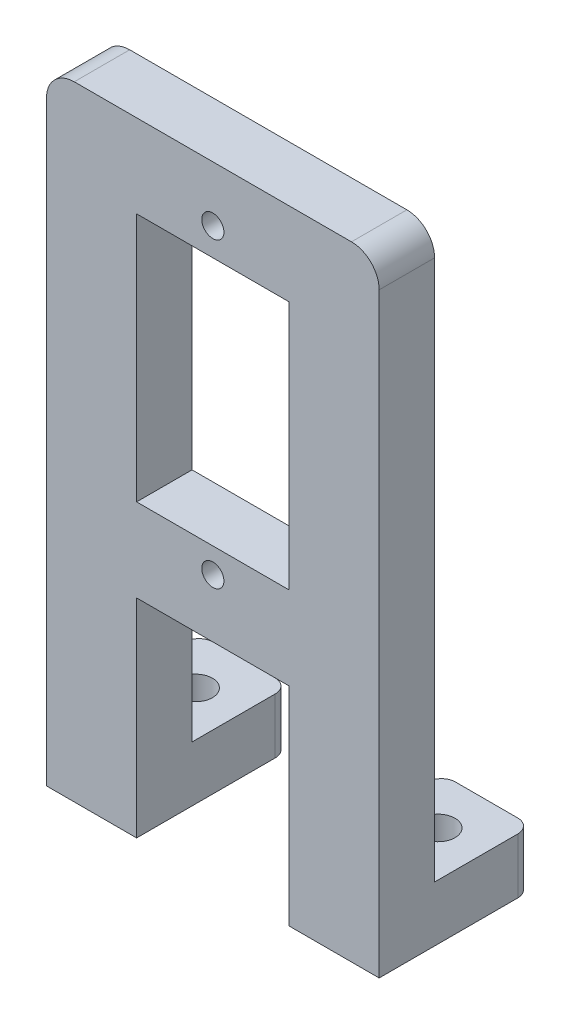
SolidWorks part; units mm, degrees
ref_plane "Front Plane" through (0, 0, 0) normal (0, 0, 1) x (1, 0, 0)
ref_plane "Top Plane" through (0, 0, 0) normal (0, 1, 0) x (1, 0, 0)
ref_plane "Right Plane" through (0, 0, 0) normal (1, 0, 0) x (0, 0, -1)
sketch "Sketch1" plane through (0, 0, 0) normal (0, 0, 1) x (1, 0, 0)
  line L0 (-15.24, -19.05) -> (-15.24, -38.1)
  line L1 (-6.985, 11.43) -> (6.985, 11.43)
  line L2 (-6.985, 11.43) -> (-6.985, -11.43)
  line L3 (-6.985, -11.43) -> (6.985, -11.43)
  line L4 (6.985, 11.43) -> (6.985, -11.43)
  line L5 (-15.24, 19.05) -> (15.24, 19.05)
  line L6 (-15.24, 19.05) -> (-15.24, -19.05)
  line L7 (-15.24, -19.05) -> (15.24, -19.05)
  line L8 (15.24, 19.05) -> (15.24, -19.05)
  line L9 (-15.24, -38.1) -> (-6.985, -38.1)
  line L10 (-6.985, -38.1) -> (-6.985, -19.05)
  line L11 (-15.24, -19.05) -> (-6.985, -19.05)
  line L12 (15.24, -19.05) -> (15.24, -38.1)
  line L13 (15.24, -38.1) -> (6.985, -38.1)
  line L14 (6.985, -38.1) -> (6.985, -19.05)
  line L15 (6.985, -19.05) -> (15.24, -19.05)
  point P5 (0, 11.43)
  point P6 (-6.985, 0)
  point P12 (0, 19.05)
  point P13 (-15.24, 0)
  dimension "D1" = 13.97
  dimension "D2" = 22.86
  dimension "D3" = 30.48
  dimension "D4" = 38.1
  dimension "D5" = 19.05
extrude "Boss-Extrude1" add sketch "Sketch1" along normal blind 5.08 contours L6 L5 L8 L7 | L11 L10 L9 L0 | L12 L13 L14 L15 | L2 L1 L4 L3
fillet "Fillet1" radius 2.54 2 edges at (15.24, 19.05, 2.54) (-15.24, 19.05, 2.54)
ref_plane "Plane1" through (0, -38.1, 0) normal (0, 1, 0) x (1, 0, 0)
sketch "Sketch3" plane through (0, -38.1, 0) normal (0, 1, 0) x (1, 0, 0)
  line L0 (-15.24, 0) -> (-15.24, 8.89)
  line L1 (-15.24, 8.89) -> (-6.985, 8.89)
  line L2 (-6.985, 8.89) -> (-6.985, 0)
  line L3 (-12.7, 0) -> (12.7, 0) construction
  line L4 (-6.985, 0) -> (-15.24, 0)
  line L5 (-15.24, 0) -> (-6.985, 0) construction
  dimension "D2" = 8.89
extrude "Boss-Extrude2" add sketch "Sketch3" along normal blind 5.08
sketch "Sketch5" plane through (0, 0, 5.08) normal (0, 0, 1) x (1, 0, 0)
  line L2 (-6.985, 11.43) -> (6.985, 11.43) construction
  circle A0 centre (0, 13.97) radius 1.016
  circle A1 centre (0, -13.716) radius 1.016
  point P4 (0, 13.802)
  point P6 (0, 14.3392)
  dimension "D1" = 2.032
  dimension "D2" = 2.032
  dimension "D3" = 27.686
  dimension "D4" = 2.54
extrude "Cut-Extrude1" cut sketch "Sketch5" against normal blind 5.08
sketch "Sketch6" plane through (0, -33.02, 0) normal (0, 1, 0) x (1, 0, 0)
  line L0 (-15.24, 8.89) -> (-15.24, 0) construction
  line L1 (-6.985, 8.89) -> (-15.24, 8.89) construction
  circle A0 centre (-11.1125, 4.445) radius 1.55
  point P4 (-15.24, 4.445)
  point P7 (-11.1125, 8.89)
  dimension "D1" = 3.1
extrude "Cut-Extrude2" cut sketch "Sketch6" against normal blind 5.08
mirror "Mirror2" about plane through (0, 0, 0) normal (1, 0, 0) of "Cut-Extrude2", "Boss-Extrude2"
fillet "Fillet2" radius 1.27 4 edges at (-6.985, -35.56, -8.89) (15.24, -35.56, -8.89) (6.985, -35.56, -8.89) (-15.24, -35.56, -8.89)
